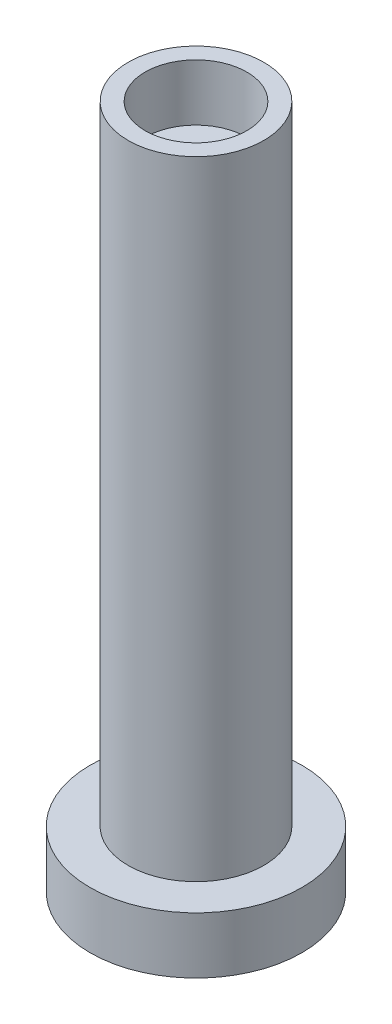
SolidWorks part; units mm, degrees
ref_plane "Front Plane" through (0, 0, 0) normal (0, 0, 1) x (1, 0, 0)
ref_plane "Top Plane" through (0, 0, 0) normal (0, 1, 0) x (1, 0, 0)
ref_plane "Right Plane" through (0, 0, 0) normal (1, 0, 0) x (0, 0, -1)
sketch "Sketch1" plane through (0, 0, 0) normal (0, 1, 0) x (1, 0, 0)
  circle A0 centre (0, 0) radius 4.8
  circle A1 centre (0, 0) radius 7.5
  dimension "D1" = 9.6
  dimension "D2" = 15
extrude "Boss-Extrude1" add sketch "Sketch1" along normal blind 44.45 contours A0 region at (0, 0, 0)
extrude "Boss-Extrude2" add sketch "Sketch1<4>" against normal blind 4 contours A0 | A1 A0 region at (0, 0, 0) region at (-7.2879, 0, 0)
sketch "Sketch1<4>" plane through (0, 0, 0) normal (0, 1, 0) x (1, 0, 0) same geometry as "Sketch1"
sketch "Sketch2" plane through (0, 44.45, 0) normal (0, 1, 0) x (1, 0, 0)
  circle A0 centre (0, 0) radius 3.6
  dimension "D1" = 7.2
extrude "Cut-Extrude1" cut sketch "Sketch2" against normal blind 4
